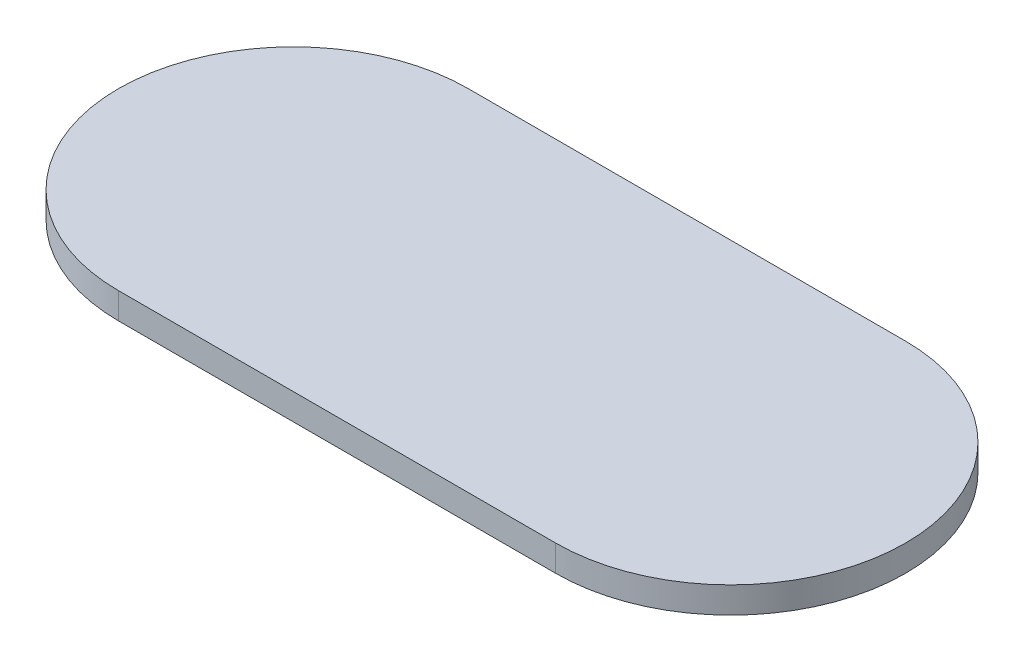
SolidWorks part; units mm, degrees
ref_plane "Front Plane" through (0, 0, 0) normal (0, 0, 1) x (1, 0, 0)
ref_plane "Top Plane" through (0, 0, 0) normal (0, 1, 0) x (1, 0, 0)
ref_plane "Right Plane" through (0, 0, 0) normal (1, 0, 0) x (0, 0, -1)
sketch "Sketch1" plane through (0, 0, 0) normal (0, 1, 0) x (1, 0, 0)
  line L1 (-31.75, -25.4) -> (31.75, -25.4)
  line L3 (-31.75, 25.4) -> (31.75, 25.4)
  line L5 (-31.75, -25.4) -> (31.75, 25.4) construction
  line L6 (-31.75, 25.4) -> (31.75, -25.4) construction
  arc A0 (-31.75, 25.4) -> (-31.75, -25.4) centre (-31.75, 0) ccw
  arc A1 (31.75, 25.4) -> (31.75, -25.4) centre (31.75, 0) cw
  point P0 (0, 0)
  point P8 (-57.15, 0)
  point P9 (57.15, 0)
  dimension "D1" = 50.8
  dimension "D2" = 114.3
extrude "Boss-Extrude1" add sketch "Sketch1" along normal blind 3.81
